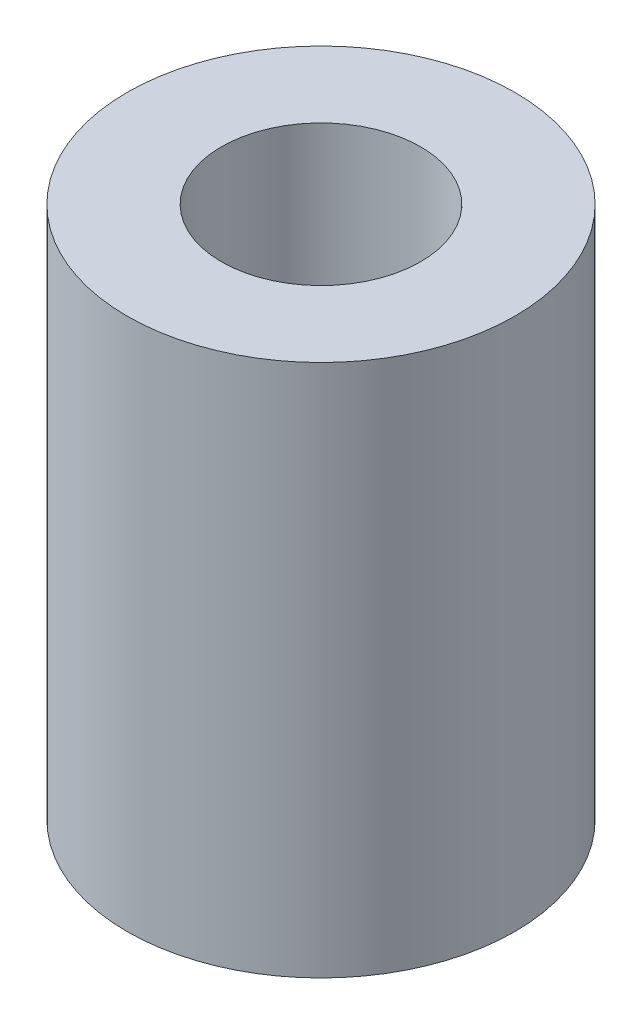
SolidWorks part; units mm, degrees
material "PLA"
ref_plane "Front Plane" through (0, 0, 0) normal (0, 0, 1) x (1, 0, 0)
ref_plane "Top Plane" through (0, 0, 0) normal (0, 1, 0) x (1, 0, 0)
ref_plane "Right Plane" through (0, 0, 0) normal (1, 0, 0) x (0, 0, -1)
sketch "Sketch1" plane through (0, 0, 0) normal (0, 1, 0) x (1, 0, 0)
  circle A0 centre (0, 0) radius 6.35
  circle A1 centre (0, 0) radius 3.2639
  dimension "D1" = 12.7
  dimension "D2" = 6.5278
extrude "Boss-Extrude1" add sketch "Sketch1" along normal blind 17.4625
